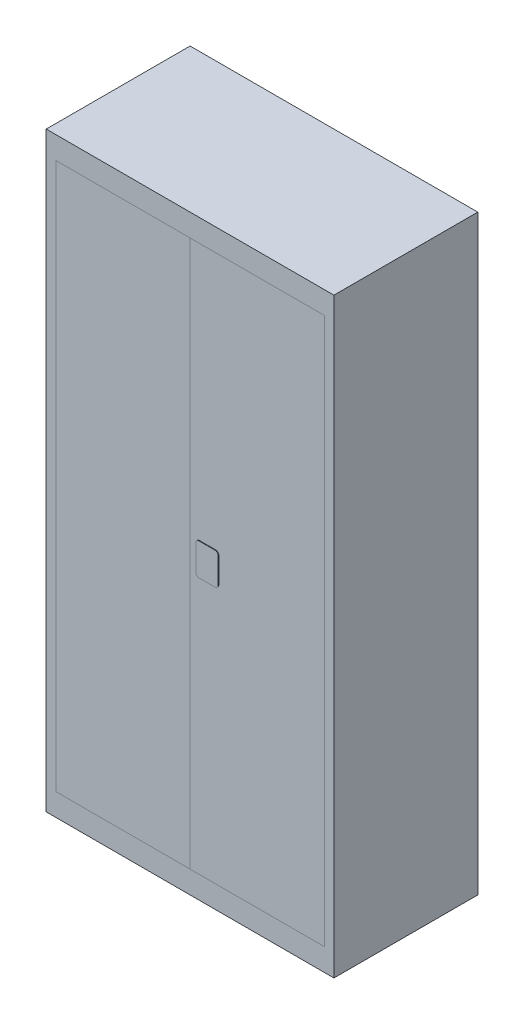
SolidWorks part; units mm, degrees
ref_plane "Front Plane" through (0, 0, 0) normal (0, 0, 1) x (1, 0, 0)
ref_plane "Top Plane" through (0, 0, 0) normal (0, 1, 0) x (1, 0, 0)
ref_plane "Right Plane" through (0, 0, 0) normal (1, 0, 0) x (0, 0, -1)
sketch "Sketch1" plane through (0, 0, 0) normal (0, 0, 1) x (1, 0, 0)
  line L1 (0, 0) -> (900, 0)
  line L2 (0, 0) -> (0, 1850)
  line L3 (0, 1850) -> (900, 1850)
  line L4 (900, 0) -> (900, 1850)
  dimension "D1" = 900
  dimension "D2" = 1850
extrude "Boss-Extrude1" add sketch "Sketch1" against normal blind 450
sketch "Sketch2" plane through (0, 0, 0) normal (0, 0, 1) x (1, 0, 0)
  line L0 (900, 1850) -> (0, 1850) construction
  line L1 (30, 1780) -> (870, 1780)
  line L2 (30, 1780) -> (30, 70)
  line L3 (30, 70) -> (870, 70)
  line L4 (870, 1780) -> (870, 70)
  line L5 (0, 0) -> (900, 0) construction
  line L6 (900, 0) -> (900, 1850) construction
  line L7 (0, 1850) -> (0, 0) construction
  line L8 (450, 1780) -> (450, 70)
  dimension "D1" = 70
  dimension "D2" = 70
  dimension "D3" = 30
  dimension "D4" = 30
extrude "Cut-Extrude1" cut sketch "Sketch2" against normal blind 20 contours L8 L1 L2 L3 | L1 L8 L3 L4 region at (240, 925, 0) region at (660, 925, 0)
extrude "Boss-Extrude2" add sketch "Sketch2<3>" along normal blind 20 from offset 20 separate body contours L8 L1 L2 L3 region at (240, 925, 0) offset against normal yes
sketch "Sketch2<3>" plane through (0, 0, 0) normal (0, 0, 1) x (1, 0, 0) same geometry as "Sketch2"
extrude "Boss-Extrude3" add sketch "Sketch2<4>" along normal blind 20 from offset 20 separate body contours L1 L8 L3 L4 region at (660, 925, 0) offset against normal yes
sketch "Sketch2<4>" plane through (0, 0, 0) normal (0, 0, 1) x (1, 0, 0) same geometry as "Sketch2"
sketch "Sketch3" plane through (0, 0, 0) normal (0, 0, 1) x (1, 0, 0)
  line L1 (480, 975) -> (530, 975)
  line L2 (470, 965) -> (470, 885)
  line L3 (480, 875) -> (530, 875)
  line L4 (540, 965) -> (540, 885)
  line L5 (900, 0) -> (900, 1850) construction
  line L6 (450, 1780) -> (450, 70) construction
  arc A0 (470, 885) -> (480, 875) centre (480, 885) ccw
  arc A1 (530, 875) -> (540, 885) centre (530, 885) ccw
  arc A2 (530, 975) -> (540, 965) centre (530, 965) cw
  arc A3 (480, 975) -> (470, 965) centre (480, 965) ccw
  point P4 (900, 925)
  point P7 (540, 925)
  point P10 (450, 925)
  point P15 (540, 875)
  point P18 (540, 975)
  point P21 (470, 975)
  dimension "D4" = 10
  dimension "D1" = 20
  dimension "D2" = 100
  dimension "D3" = 70
extrude "Boss-Extrude4" add sketch "Sketch3" along normal blind 2
